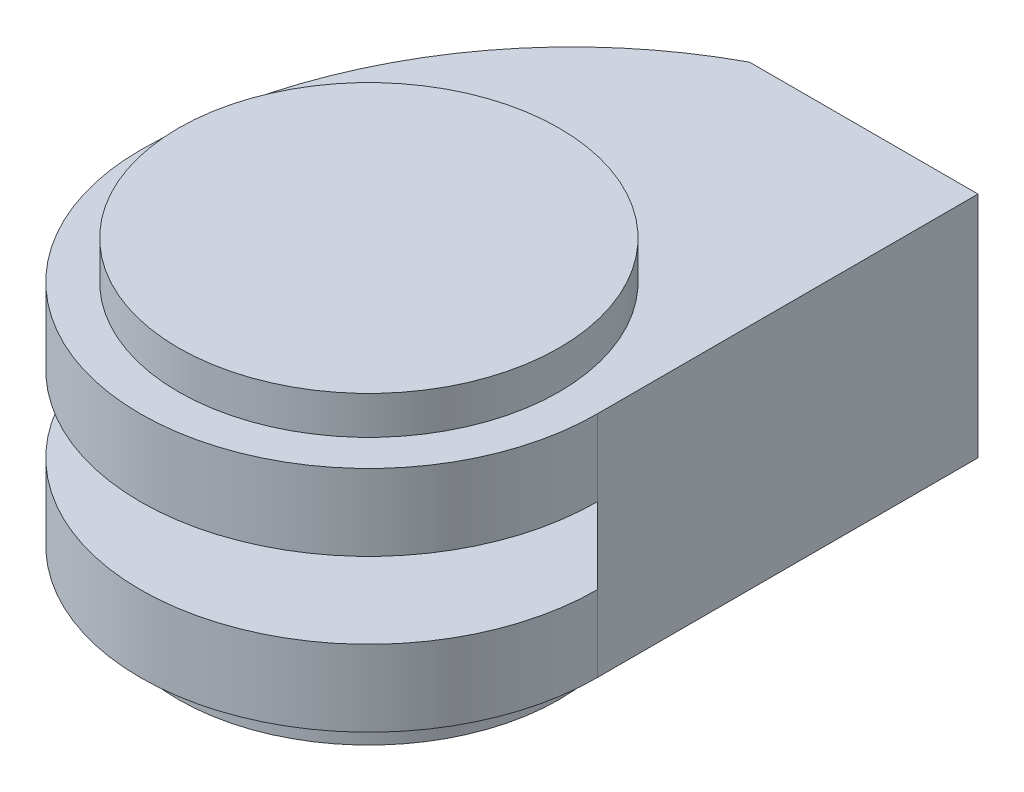
SolidWorks part; units mm, degrees
ref_plane "Front Plane" through (0, 0, 0) normal (0, 0, 1) x (1, 0, 0)
ref_plane "Top Plane" through (0, 0, 0) normal (0, 1, 0) x (1, 0, 0)
ref_plane "Right Plane" through (0, 0, 0) normal (1, 0, 0) x (0, 0, -1)
sketch "Sketch1" plane through (0, 0, 0) normal (0, 1, 0) x (1, 0, 0)
  line L0 (3, -2.5) -> (3, 2.5)
  line L1 (3, 2.5) -> (10.2991, 2.5) construction
  line L2 (0, -2.5) -> (0, 0) construction
  line L3 (3, 2.5) -> (0, 2.5)
  line L4 (0, -2.5) -> (-3, -2.5) construction
  circle A0 centre (0, -2.5) radius 3
  arc A1 (-2.7692, -1.3462) -> (3, 2.5) centre (3, -3.75) cw construction
  arc A2 (0, 2.5) -> (-3, -2.5) centre (2.6667, -2.5) ccw
  dimension "D1" = 6
  dimension "D4" = 2.5
  dimension "D2" = 8
  dimension "D3" = 6
  dimension "D5" = 3
extrude "Boss-Extrude1" add sketch "Sketch1" along normal blind 1.5 and the other way blind 1.5 contours A0 | A1 A0 L0 region at (0.8079, 0, -1.0066) region at (0, 0, 2.5)
sketch "Sketch2" plane through (0, 0, 0) normal (0, 1, 0) x (1, 0, 0)
  line L0 (-3, -2.5) -> (-3, 4.7426)
  line L1 (-3, 4.7426) -> (2.1213, -0.3787)
  line L3 (3, -2.5) -> (3, 2.5) construction
  circle A0 centre (0, -2.5) radius 3
  arc A1 (-3, -2.5) -> (3, -2.5) centre (0, -2.5) ccw construction
  dimension "D1" = 45
extrude "Cut-Extrude1" cut sketch "Sketch2" against normal blind 0.5 and the other way blind 0.5 contours A0 | A0 region at (-1.667, 0, -1.5246) region at (0, 0, 2.5)
sketch "Sketch3" plane through (0, 1.5, 0) normal (0, 1, 0) x (1, 0, 0)
  circle A0 centre (0, -2.5) radius 2.5
  dimension "D1" = 5
extrude "Boss-Extrude2" add sketch "Sketch3" along normal blind 0.5
sketch "Sketch4" plane through (0, -1.5, 0) normal (0, -1, 0) x (1, 0, 0)
  circle A0 centre (0, 2.5) radius 2.5 construction
  circle A1 centre (0, 2.5) radius 2.5
extrude "Boss-Extrude3" add sketch "Sketch4" along normal blind 0.5
